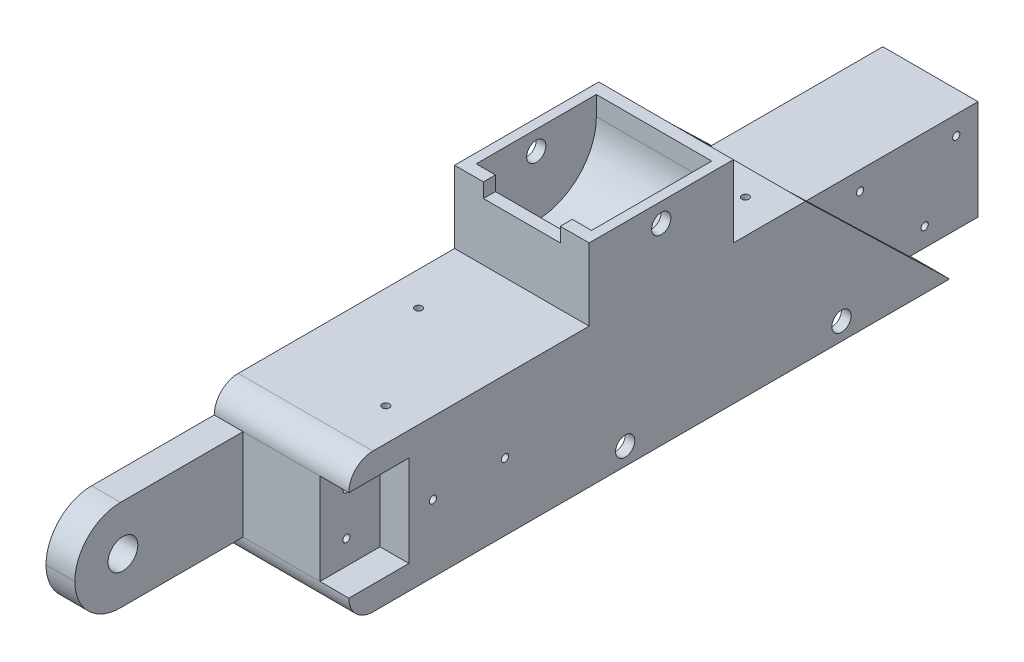
SolidWorks part; units mm, degrees
ref_plane "前视基准面" through (0, 0, 0) normal (0, 0, 1) x (1, 0, 0)
ref_plane "上视基准面" through (0, 0, 0) normal (0, 1, 0) x (1, 0, 0)
ref_plane "右视基准面" through (0, 0, 0) normal (1, 0, 0) x (0, 0, -1)
other "Configuration Table"
sketch "草图1" plane through (0, 0, 0) normal (1, 0, 0) x (0, 0, -1)
  line L0 (-150, 0) -> (150, 0) construction
  line L1 (-125, 14.5) -> (125, 14.5)
  line L2 (-125, 14.5) -> (-125, -14.5)
  line L3 (-125, -14.5) -> (125, -14.5)
  line L4 (125, 14.5) -> (125, -14.5)
  line L5 (-72.5, 29.5) -> (-72.5, 25.5)
  line L6 (-75, 14.5) -> (-45, 14.5)
  line L7 (-75, 14.5) -> (-75, 29.5)
  line L8 (-120, 10.8586) -> (120, 10.8586)
  line L9 (-120, 10.8586) -> (-120, -10.8586)
  line L10 (-120, -10.8586) -> (120, -10.8586)
  line L11 (120, 10.8586) -> (120, -10.8586)
  line L12 (-120, 10.8586) -> (120, -10.8586) construction
  line L13 (-120, -10.8586) -> (120, 10.8586) construction
  line L14 (-75, 29.5) -> (-45, 29.5)
  line L15 (-45, 14.5) -> (-45, 29.5)
  line L16 (-15, 14.5) -> (15, 14.5)
  line L17 (-15, 14.5) -> (-15, 29.5)
  line L18 (-15, 29.5) -> (15, 29.5)
  line L19 (15, 14.5) -> (15, 29.5)
  line L20 (45, 14.5) -> (75, 14.5)
  line L21 (45, 14.5) -> (45, 29.5)
  line L22 (45, 29.5) -> (75, 29.5)
  line L23 (75, 14.5) -> (75, 29.5)
  line L24 (-47.5, 29.5) -> (-47.5, 25.5)
  line L25 (-12.5, 29.5) -> (-12.5, 25.5)
  line L26 (12.5, 29.5) -> (12.5, 25.5)
  line L27 (47.5, 29.5) -> (47.5, 25.5)
  line L29 (72.5, 25.5) -> (72.5, 29.5)
  circle A2 centre (-67.5, -10.8586) radius 2
  circle A3 centre (-22.5, -10.8586) radius 2
  circle A4 centre (22.5, -10.8586) radius 2
  circle A5 centre (-60, 25.5) radius 2
  circle A6 centre (67.5, -10.8586) radius 2
  circle A7 centre (0, 25.5) radius 2
  circle A8 centre (60, 25.5) radius 2
  circle A9 centre (-60, 25.5) radius 12.5
  circle A10 centre (0, 25.5) radius 12.5
  circle A11 centre (60, 25.5) radius 12.5
  circle A12 centre (-67.5, -10.8586) radius 12.5
  circle A13 centre (-22.5, -10.8586) radius 12.5
  circle A14 centre (22.5, -10.8586) radius 12.5
  circle A15 centre (67.5, -10.8586) radius 12.5
  circle A16 centre (150, 0) radius 2
  circle A17 centre (-150, 0) radius 2
  circle A18 centre (-150, 0) radius 3.1
  point P10 (0, 0)
  point P12 (-125, 0)
  point P56 (-60, 29.5)
  point P62 (0, 29.5)
  point P64 (60, 29.5)
  dimension "D2" = 5
  dimension "D4" = 25
  dimension "D8" = 4
  dimension "D18" = 4
  dimension "D22" = 6.2
  dimension "D1" = 300
  dimension "D3" = 5
  dimension "D5" = 14.5
  dimension "D6" = 120
  dimension "D7" = 10.8586
  dimension "D9" = 52.5
  dimension "D10" = 45
  dimension "D11" = 45
  dimension "D12" = 45
  dimension "D13" = 60
  dimension "D14" = 60
  dimension "D15" = 60
  dimension "D16" = 60
  dimension "D17" = 52.5
  dimension "D19" = 30
  dimension "D20" = 4
  dimension "D21" = 15
extrude "凸台-拉伸1" add sketch "草图1" along normal blind 28 contours L1 L4 L3 L2 | L14 L15 L6 L7 | L18 L19 L16 L17 | L22 L23 L20 L21
extrude "切除-拉伸1" cut sketch "草图1<3>" along normal through all contours A2 | A3 | A4 | A6 | A8 | A7 | A5
sketch "草图1<3>" plane through (0, 0, 0) normal (1, 0, 0) x (0, 0, -1) same geometry as "草图1"
extrude "切除-拉伸2" cut sketch "草图1<5>" along normal offset from surface (24 mm away) 2 from offset 2 contours A9 L14 L5 | A9 L24 L14 | A10 L18 L25 | A10 L26 L18 | A11 L22 L27 | A11 L29 L22 | A12 | A9 | A13 | A10 | A14 | A11 | A15 region at (0, 28.5053, 72.3037) region at (0, 28.5053, 47.6963) region at (0, 28.5053, 12.3037) region at (0, 28.5053, -12.3037) region at (0, 28.5053, -47.6963) region at (0, 28.5053, -72.3037) up to face at (28, -10.8586, 65.5)
sketch "草图1<5>" plane through (0, 0, 0) normal (1, 0, 0) x (0, 0, -1) same geometry as "草图1"
sketch "草图3" plane through (0, 0, 125) normal (0, 0, 1) x (1, 0, 0)
  line L0 (28, 14.5) -> (28, -14.5) construction
  line L1 (28, 9.5) -> (22, 9.5)
  line L2 (28, 9.5) -> (28, -9.5)
  line L3 (28, -9.5) -> (22, -9.5)
  line L4 (22, 9.5) -> (22, -9.5)
  line L5 (28, 14.5) -> (0, 14.5) construction
  line L6 (28, -14.5) -> (0, -14.5) construction
  line L7 (0, 14.5) -> (0, -14.5) construction
  line L8 (0, 9.5) -> (6, 9.5)
  line L9 (0, 9.5) -> (0, -9.5)
  line L10 (0, -9.5) -> (6, -9.5)
  line L11 (6, 9.5) -> (6, -9.5)
  dimension "D1" = 6
  dimension "D2" = 5
  dimension "D3" = 5
extrude "凸台-拉伸2" add sketch "草图3" along normal blind 35 contours L1 L4 L3 L2
extrude "凸台-拉伸3" add sketch "草图3<3>" along normal blind 35 contours L2 L3 L4 L1 | L9 L10 L11 L8
sketch "草图3<3>" plane through (0, 0, 125) normal (0, 0, 1) x (1, 0, 0) same geometry as "草图3"
extrude "切除-拉伸3" cut sketch "草图1<6>" along normal through all contours A17
sketch "草图1<6>" plane through (0, 0, 0) normal (1, 0, 0) x (0, 0, -1) same geometry as "草图1"
extrude "切除-拉伸7" cut sketch "草图1<8>" along normal up to next contours A18
sketch "草图1<8>" plane through (0, 0, 0) normal (1, 0, 0) x (0, 0, -1) same geometry as "草图1"
fillet "圆角1" radius 9.5 4 edges at (25, 9.5, 160) (25, -9.5, 160) (3, -9.5, 160) (3, 9.5, 160)
fillet "圆角2" radius 5 2 edges at (14, -14.5, 125) (14, 14.5, 125)
sketch "草图4" plane through (0, 0, -125) normal (0, 0, -1) x (-1, 0, 0)
  line L1 (-28, 14.5) -> (0, 14.5) construction
  circle A0 centre (-14, 0) radius 5.1
  point P7 (-14, 14.5)
  dimension "D1" = 10.2
extrude "切除-拉伸4" cut sketch "草图4" against normal blind 31.5
extrude "切除-拉伸5" cut sketch "草图4<2>" against normal offset from surface (21.5 mm away) 10 flip side to cut up to face at (8.9, 0, -93.5)
sketch "草图4<2>" plane through (0, 0, -125) normal (0, 0, -1) x (-1, 0, 0) same geometry as "草图4"
sketch "草图5" plane through (0, 0, -103.5) normal (0, 0, -1) x (-1, 0, 0)
  line L0 (-28, 14.5) -> (0, 14.5) construction
  line L1 (-25.9, -12.4) -> (-2.1, -12.4)
  line L2 (-25.9, -12.4) -> (-25.9, 12.4)
  line L3 (-25.9, 12.4) -> (-2.1, 12.4)
  line L4 (-2.1, -12.4) -> (-2.1, 12.4)
  line L5 (-25.9, -12.4) -> (-2.1, 12.4) construction
  line L6 (-25.9, 12.4) -> (-2.1, -12.4) construction
  line L7 (0, -14.5) -> (0, 14.5) construction
  circle A0 centre (-14, 0) radius 5.1 construction
  point P0 (-14, 0)
  dimension "D1" = 2.1
  dimension "D2" = 2.1
extrude "切除-拉伸6" cut sketch "草图5" against normal blind 18 flip side to cut contours L3 L4 L1 L2
sketch "草图6" plane through (0, 14.5, 0) normal (0, 1, 0) x (1, 0, 0)
  circle A0 centre (7, 23.5) radius 0.75
  circle A1 centre (21, 35.5) radius 0.75
  circle A2 centre (7, -23.5) radius 0.75
  circle A3 centre (21, -35.5) radius 0.75
  dimension "D1" = 1.5
extrude "切除-拉伸8" cut sketch "草图6" against normal blind 4 contours A2 | A3 | A0 | A1
sketch "草图7" plane through (0, 14.5, 0) normal (0, 1, 0) x (1, 0, 0)
  circle A0 centre (7, -89.5) radius 0.75
  circle A1 centre (21.2, -110.5) radius 0.75
  dimension "D1" = 1.5
extrude "切除-拉伸9" cut sketch "草图7" against normal blind 4 contours A0 | A1
sketch "草图8" plane through (0, 0, 0) normal (-1, 0, 0) x (0, 0, 1)
  circle A0 centre (47, 4) radius 0.75
  circle A1 centre (2.499, -1.5) radius 0.75
  dimension "D1" = 1.5
extrude "切除-拉伸10" cut sketch "草图8" against normal blind 4
sketch "草图9" plane through (28, 0, 0) normal (1, 0, 0) x (0, 0, -1)
  circle A0 centre (-107.5, -0.5) radius 0.75
  circle A1 centre (-92.5, -0.5) radius 0.75
  dimension "D1" = 1.5
extrude "切除-拉伸11" cut sketch "草图9" against normal blind 4 contours A0 | A1
sketch "草图10" plane through (0, 0, 0) normal (-1, 0, 0) x (0, 0, 1)
  line L0 (30, 14.5) -> (0, -14.5)
  line L1 (45, 14.5) -> (15, 14.5) construction
  line L2 (120, -14.5) -> (-85.5, -14.5) construction
  line L3 (30, 14.5) -> (30, 45.5421)
  line L4 (30, 45.5421) -> (207.4503, 45.5421)
  line L5 (207.4503, 45.5421) -> (207.4503, -65.6361)
  line L6 (207.4503, -65.6361) -> (0, -65.6361)
  line L7 (0, -65.6361) -> (0, -14.5)
  line L8 (30, 45.5421) -> (-140.4585, 45.5421)
  line L9 (30, 14.5) -> (-10, 14.5)
  line L10 (30, 14.5) -> (30, -14.5)
  line L11 (30, -14.5) -> (-10, -14.5)
  line L12 (-10, 14.5) -> (-10, -14.5)
  line L13 (-140.4585, 45.5421) -> (-140.4585, -65.6361)
  line L14 (-140.4585, -65.6361) -> (-10, -65.6361)
  line L15 (-10, -65.6361) -> (-10, -14.5)
  circle M8 centre (2.499, -1.5) radius 0.75
  circle M12 centre (0, 25.5) radius 2
  circle M13 centre (-60, 25.5) radius 2
  circle M14 centre (-67.5, -10.8586) radius 2
  circle M15 centre (-22.5, -10.8586) radius 2
  line M17 (-85.5, 14.5) -> (-85.5, -14.5)
  line M18 (-85.5, -14.5) -> (120, -14.5)
  line M29 (45, 14.5) -> (15, 14.5)
  line M30 (15, 14.5) -> (15, 29.5)
  line M31 (15, 29.5) -> (-15, 29.5)
  line M32 (-15, 29.5) -> (-15, 14.5)
  line M33 (-15, 14.5) -> (-45, 14.5)
  line M34 (-45, 14.5) -> (-45, 29.5)
  line M35 (-45, 29.5) -> (-75, 29.5)
  line M36 (-75, 29.5) -> (-75, 14.5)
  line M37 (-75, 14.5) -> (-85.5, 14.5)
  dimension "D1" = 40
sketch "草图11" plane through (0, 0, 0) normal (1, 0, 0) x (0, 0, -1)
  line L0 (-30, 14.5) -> (0, -14.5) construction
  line L1 (-45, 14.5) -> (-15, 14.5) construction
  line L2 (-120, -14.5) -> (85.5, -14.5) construction
  circle A0 centre (-14.5301, 6.5) radius 0.75
  circle A1 centre (-1.0818, -6.5) radius 0.75
  circle A2 centre (-14.5301, 6.5) radius 2.5
  circle A3 centre (-1.0818, -6.5) radius 2.5
  circle A4 centre (-14.5301, 6.5) radius 1.8
  circle A5 centre (-1.0818, -6.5) radius 1.8
  circle A6 centre (5.4699, 6.5) radius 0.75
  circle A7 centre (5.4699, 6.5) radius 2.5
  circle A8 centre (5.4699, 6.5) radius 1.8
  dimension "D3" = 1.5
  dimension "D4" = 3.6
  dimension "D5" = 5
  dimension "D1" = 5
  dimension "D2" = 5
  dimension "D6" = 8
  dimension "D7" = 8
  dimension "D8" = 20
extrude "切除-拉伸12" cut sketch "草图11" along normal through all contours A1 | A0 | A6
extrude "切除-拉伸14" cut sketch "草图10" against normal through all contours L14 L15 L3 L8 L13 M18 M17 M37 M36 M35 M34 M33 M32 M31 M30 M29 | L12 L9 M30 M31 M32 M33 M34 M35 M36 M37 M17 M18 M12 M14 M15 M13 region at (0, 16.5351, 22.5) region at (0, 6.3937, -42.6633)
extrude "切除-拉伸15" cut sketch "草图10<5>" against normal blind 4.1 contours L9 L12 L0 M18 M29 M8 region at (0, 2.9108, 4.0037)
sketch "草图10<5>" plane through (0, 0, 0) normal (-1, 0, 0) x (0, 0, 1) same geometry as "草图10"
extrude "切除-拉伸16" cut sketch "草图10<6>" along normal blind 4.1 from surface contours L9 L12 L0 M18 M29 M8 | M8 region at (0, 2.9108, 4.0037) region at (0, -1.5, 2.499) starting at face at (28, 6.7692, 90.5389)
sketch "草图10<6>" plane through (0, 0, 0) normal (-1, 0, 0) x (0, 0, 1) same geometry as "草图10"
sketch "草图13" plane through (0, 14.5, 0) normal (0, 1, 0) x (1, 0, 0)
  line L0 (4.1, -30) -> (0, -30) construction
  line L1 (4.1, -30) -> (23.9, -30)
  line L2 (4.1, -30) -> (4.1, 10)
  line L3 (4.1, 10) -> (23.9, 10)
  line L4 (23.9, -30) -> (23.9, 10)
  line L5 (4.1, -30) -> (4.1, -5.9372) construction
extrude "切除-拉伸17" cut sketch "草图13" against normal blind 4.1
sketch "草图14" plane through (0, -14.5, 0) normal (0, -1, 0) x (1, 0, 0)
  line L0 (4.1, 0) -> (0, 0) construction
  line L1 (4.1, 0) -> (23.9, 0)
  line L2 (4.1, 0) -> (4.1, -10)
  line L3 (4.1, -10) -> (23.9, -10)
  line L4 (23.9, 0) -> (23.9, -10)
  line L5 (4.1, -10) -> (4.1, 0) construction
extrude "切除-拉伸18" cut sketch "草图14" against normal blind 4.1
sketch "草图15" plane through (0, 0, 0) normal (-1, 0, 0) x (0, 0, 1)
  line L0 (0, -10.4) -> (0, -14.5)
  line L1 (0, -14.5) -> (4.2414, -10.4)
  line L2 (30, 14.5) -> (0, -14.5) construction
  line L4 (4.2414, -10.4) -> (0, -10.4)
  line L5 (0, -10.4) -> (-10, -10.4) construction
extrude "切除-拉伸19" cut sketch "草图15" against normal through all
sketch "草图16" plane through (0, 29.5, 0) normal (0, 1, 0) x (1, 0, 0)
  line L0 (28, -75) -> (0, -75) construction
  line L1 (6, -77.5) -> (22, -77.5)
  line L2 (6, -77.5) -> (6, -72.5)
  line L3 (6, -72.5) -> (22, -72.5)
  line L4 (22, -77.5) -> (22, -72.5)
  line L5 (6, -77.5) -> (22, -72.5) construction
  line L6 (6, -72.5) -> (22, -77.5) construction
  line L7 (26, -72.5) -> (2, -72.5) construction
  line L8 (26, -47.5) -> (26, -72.5) construction
  line L9 (6, -72.5) -> (22, -72.5)
  line L10 (6, -72.5) -> (6, -60)
  line L11 (6, -60) -> (22, -60)
  line L12 (22, -72.5) -> (22, -60)
  point P0 (14, -75)
  point P7 (14, -75)
  point P14 (26, -60)
  line M10 (0, -75) -> (28, -75)
  line M13 (26, -72.5) -> (2, -72.5)
  dimension "D1" = 16
extrude "切除-拉伸20" cut sketch "草图16" against normal blind 3 contours L1 L4 L2 M10 | L4 L2 M10 M13 | L12 L11 L10 M13 region at (14, 29.5, 76.25) region at (14, 29.5, 73.75) region at (14, 29.5, 66.25)
sketch "草图18" plane through (28, 0, 0) normal (1, 0, 0) x (0, 0, -1)
  line L0 (-150.5, 9.5) -> (-125, 9.5) construction
  line L1 (-160, 9.5) -> (-112.5, 9.5)
  line L2 (-160, 9.5) -> (-160, -9.5)
  line L3 (-160, -9.5) -> (-112.5, -9.5)
  line L4 (-112.5, 9.5) -> (-112.5, -9.5)
  line L5 (-150.5, -9.5) -> (-125, -9.5) construction
  arc A0 (-150.5, 9.5) -> (-160, 0) centre (-150.5, 0) ccw construction
  circle A1 centre (-107.5, -0.5) radius 0.75 construction
  circle A2 centre (-119.5, 4.5) radius 1.5
  circle A3 centre (-119.5, 4.5) radius 0.75
  circle A4 centre (-119.5, 4.5) radius 2.25
  circle A5 centre (-119.5, -4.5) radius 0.75
  circle A6 centre (-119.5, -4.5) radius 1.5
  circle A7 centre (-119.5, -4.5) radius 2.25
  dimension "D1" = 5
  dimension "D2" = 4.5
  dimension "D3" = 3
  dimension "D4" = 1.5
  dimension "D5" = 7
  dimension "D6" = 5
  dimension "D7" = 5
extrude "切除-拉伸21" cut sketch "草图18" against normal up to surface (6 mm away) contours L1 L4 L3 L2 up to face at (22, 2, 150)
extrude "切除-拉伸22" cut sketch "草图18<3>" against normal blind 4 from surface contours A3 | A5 starting at face at (22, 0, 118.75)
sketch "草图18<3>" plane through (28, 0, 0) normal (1, 0, 0) x (0, 0, -1) same geometry as "草图18"
ref_plane "基准面1" through (-10, 0, 0) normal (1, 0, 0) x (0, 0, -1)
sketch "草图17" plane through (-10, 0, 0) normal (1, 0, 0) x (0, 0, -1)
  line L1 (-200, -100) -> (200, -100)
  line L2 (-200, -100) -> (-200, 100)
  line L3 (-200, 100) -> (200, 100)
  line L4 (200, -100) -> (200, 100)
  line L5 (-200, -100) -> (200, 100) construction
  line L6 (-200, 100) -> (200, -100) construction
  point P0 (0, 0)
  dimension "D1" = 400
  dimension "D2" = 200
